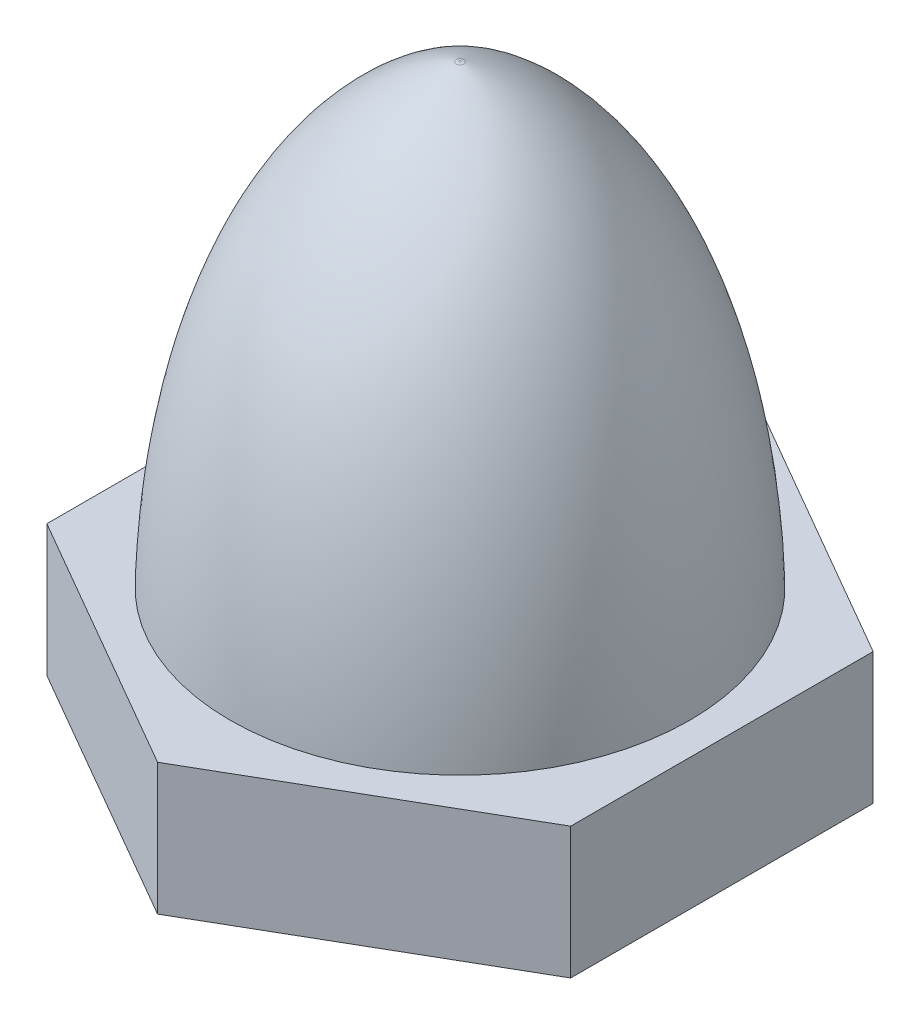
SolidWorks part; units mm, degrees
material "Aleación 1060"
ref_plane "Alzado" through (0, 0, 0) normal (0, 0, 1) x (1, 0, 0)
ref_plane "Planta" through (0, 0, 0) normal (0, 1, 0) x (1, 0, 0)
ref_plane "Vista lateral" through (0, 0, 0) normal (1, 0, 0) x (0, 0, -1)
sketch "Croquis1" plane through (0, 0, 0) normal (0, 1, 0) x (1, 0, 0)
  line L1 (0, -6.9) -> (5.9756, -3.45)
  line L2 (5.9756, -3.45) -> (5.9756, 3.45)
  line L3 (5.9756, 3.45) -> (0, 6.9)
  line L4 (0, 6.9) -> (-5.9756, 3.45)
  line L5 (-5.9756, 3.45) -> (-5.9756, -3.45)
  line L6 (-5.9756, -3.45) -> (0, -6.9)
  circle A0 centre (0, 0) radius 5.9756 construction
  dimension "D2" = 11.9512
  dimension "D1" = 6.9
extrude "Saliente-Extruir1" add sketch "Croquis1" along normal blind 3
sketch "Croquis2" plane through (0, 3, 0) normal (0, 1, 0) x (1, 0, 0)
  circle A0 centre (0, 0) radius 5.5
  dimension "D1" = 11
extrude "Saliente-Extruir2" add sketch "Croquis2" along normal blind 10.4
ref_plane "Plano1" through (0, 0, 0) normal (-0.5, 0, 0.866) x (0.866, 0, 0.5)
sketch "Croquis3" plane through (0, 0, 0) normal (-0.5, 0, 0.866) x (0.866, 0, 0.5)
  line L0 (-0.0551, 13.4) -> (-9.0657, 13.4)
  line L1 (0, 16.4) -> (0, 1.0046) construction
  line L2 (-9.0657, 13.4) -> (-9.0657, 3)
  line L4 (-9.0657, 3) -> (-5.2428, 3)
  spline S0 degree 3 poles (-0.0551, 13.4) (-3.553, 12.1955) (-5.1294, 7.5918) (-5.2428, 3) knots 0.003431 0.003431 0.003431 0.003431 0.878427 0.878427 0.878427 0.878427
  dimension "D1" = 10.4
ref_axis "Eje1" through (0, 13.4, 0) along (0, -1, 0)
revolve "Cortar-Revolución17" cut sketch "Croquis3" angle 360 about L1
fillet "Redondeo3" radius 0.2 1 edges at (-0.0551, 13.4, 0)
sketch "Croquis4" plane through (0, 0, 0) normal (0, -1, 0) x (1, 0, 0)
  circle A0 centre (0, 0) radius 2.5
extrude "Cortar-Extruir1" cut sketch "Croquis4" against normal blind 10
